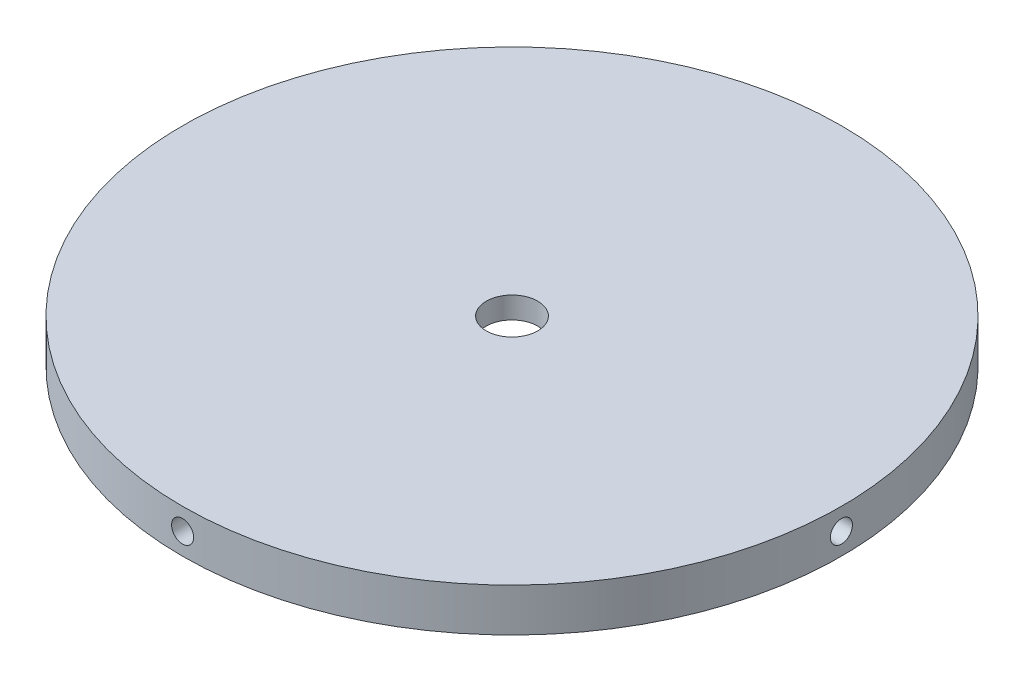
SolidWorks part; units mm, degrees
material "6061-T6 (SS)"
ref_plane "Front Plane" through (0, 0, 0) normal (0, 0, 1) x (1, 0, 0)
ref_plane "Top Plane" through (0, 0, 0) normal (0, 1, 0) x (1, 0, 0)
ref_plane "Right Plane" through (0, 0, 0) normal (1, 0, 0) x (0, 0, -1)
sketch "Sketch2" plane through (0, 0, 0) normal (0, 1, 0) x (1, 0, 0)
  circle A0 centre (0, 0) radius 76.1746
  dimension "D1" = 152.3492
extrude "Boss-Extrude1" add sketch "Sketch2" along normal blind 10
sketch "Sketch3" plane through (0, 10, 0) normal (0, 1, 0) x (1, 0, 0)
  circle A0 centre (0, 0) radius 5.9531
  dimension "D1" = 11.9062
extrude "Cut-Extrude1" cut sketch "Sketch3" against normal through all both and the other way through all
ref_plane "Plane2" through (0, 5, 0) normal (0, 1, 0) x (1, 0, 0)
sketch "Sketch7" plane through (0, 5, 0) normal (0, 1, 0) x (1, 0, 0)
  line L0 (-76.1746, 0) -> (76.1746, 0) construction
  line L1 (0, -76.1746) -> (0, 76.1746) construction
  circle A0 centre (0, 0) radius 76.1746 construction
  point P5 (-76.1746, 0)
  point P6 (0, 0)
  point P9 (0, 0)
ref_plane "Plane3" through (-76.1746, 0, 0) normal (1, 0, 0) x (0, 0, -1)
sketch "Sketch9" plane through (-76.1746, 0, 0) normal (1, 0, 0) x (0, 0, -1)
  point P0 (0, 5)
hole_wizard "1/4-20 Tapped Hole1" positions "Sketch9" profile "Sketch10" tap size "1/4-20" standard "ANSI Inch"
sketch "Sketch10" plane through (-76.1746, 5, 0) normal (0, 1, 0) x (0, 0, 1)
  line L0 (0, 0) -> (0, 26.9338)
  line L1 (0, 26.9338) -> (2.5527, 25.4)
  line L2 (2.5527, 25.4) -> (2.5527, 0)
  line L5 (2.5527, 0) -> (0, 0)
  line L10 (0, 26.9338) -> (-2.5527, 25.4) construction
  line L11 (0, -6.35) -> (0, 107.95) construction
  dimension "Tap Drill Dia." = 5.1054
  dimension "Tap Drill Depth" = 25.4
  dimension "Drill Angle" = 118
cosmetic thread "Hole Thread1" parameters "D1"=12.7, "D2"=6.35
pattern_circular "CirPattern2" count 4 over 270 about axis through (0, 10, 0) along (0, -1, 0) of "1/4-20 Tapped Hole1"
sketch "Sketch11" plane through (0, 0, 0) normal (0, -1, 0) x (1, 0, 0)
  circle A0 centre (0, 0) radius 66.6496
  circle A1 centre (0, 0) radius 76.1746 construction
  dimension "D1" = 9.525
extrude "Cut-Extrude2" cut sketch "Sketch11" against normal offset from surface (5 mm away) 5 up to face at (0, 10, 5.9531)
